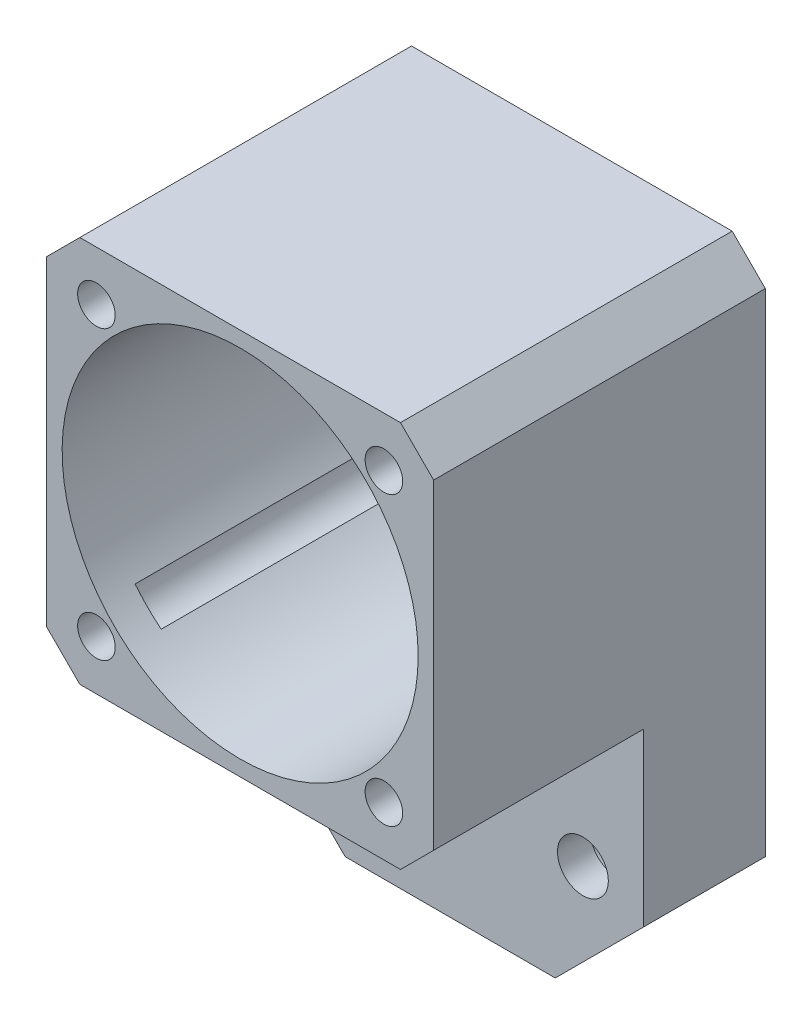
SolidWorks part; units mm, degrees
material "S235JR"
ref_plane "xy" through (0, 0, 0) normal (0, 0, 1) x (1, 0, 0)
ref_plane "xz" through (0, 0, 0) normal (0, 1, 0) x (1, 0, 0)
ref_plane "yz" through (0, 0, 0) normal (1, 0, 0) x (0, 0, -1)
ref_axis "x" through (-22.55, 0, 0) along (1, 0, 0)
ref_axis "y" through (0, 24.15, 0) along (0, -1, 0)
ref_axis "z" through (0, 0, -1.65) along (0, 0, 1)
sketch "Skizze1" plane through (0, 0, 0) normal (0, 0, 1) x (1, 0, 0)
  line L0 (-12, -28) -> (12, -28) construction
  line L1 (-17.5, 17.5) -> (17.5, 17.5)
  line L2 (-17.5, 17.5) -> (-17.5, -38)
  line L3 (-17.5, -38) -> (17.5, -38)
  line L4 (17.5, 17.5) -> (17.5, -38)
  line L5 (-13, 13) -> (13, 13) construction
  line L6 (-13, 13) -> (-13, -13) construction
  line L7 (-13, -13) -> (13, -13) construction
  line L8 (13, 13) -> (13, -13) construction
  circle A0 centre (0, 0) radius 16.1
  circle A1 centre (-13, 13) radius 1.7
  circle A2 centre (13, 13) radius 1.7
  circle A3 centre (-13, -13) radius 1.7
  circle A4 centre (13, -13) radius 1.7
  circle A5 centre (-12, -28) radius 2.3
  circle A6 centre (12, -28) radius 2.3
  point P7 (0, -38)
  point P12 (0, 13)
  point P13 (-13, 0)
  point P23 (0, -28)
  dimension "D1" = 32.2
  dimension "D6" = 3.4
  dimension "D8" = 4.6
  dimension "D2" = 38
  dimension "D3" = 17.5
  dimension "D4" = 35
  dimension "D5" = 26
  dimension "D7" = 10
  dimension "D9" = 24
extrude "Aufsatz-Linear austragen1" add sketch "Skizze1" along normal blind 11
sketch "Skizze2" plane through (0, 0, 11) normal (0, 0, 1) x (1, 0, 0)
  line L1 (-17.5, 17.5) -> (17.5, 17.5)
  line L2 (-17.5, 17.5) -> (-17.5, -17.5)
  line L3 (-17.5, -17.5) -> (17.5, -17.5)
  line L4 (17.5, 17.5) -> (17.5, -17.5)
  circle A0 centre (0, 0) radius 16.1 construction
  circle A1 centre (0, 0) radius 16.1
  circle A2 centre (13, 13) radius 1.7 construction
  circle A3 centre (13, -13) radius 1.7 construction
  circle A4 centre (-13, -13) radius 1.7 construction
  circle A5 centre (-13, 13) radius 1.7 construction
  circle A6 centre (13, 13) radius 1.7
  circle A7 centre (13, -13) radius 1.7
  circle A8 centre (-13, -13) radius 1.7
  circle A9 centre (-13, 13) radius 1.7
extrude "Aufsatz-Linear austragen2" add sketch "Skizze2" along normal blind 19
sketch "Skizze4" plane through (0, 0, 0) normal (0, 0, 1) x (1, 0, 0)
  circle A0 centre (-12, -28) radius 4
  circle A1 centre (12, -28) radius 4
  dimension "D1" = 8
extrude "Schnitt-Linear austragen1" cut sketch "Skizze4" along normal offset from surface (8 mm away) 3 up to face at (0, -27.75, 11)
sketch "Skizze5" plane through (0, 0, 0) normal (0, 0, 1) x (1, 0, 0)
  circle A0 centre (-13, 13) radius 2.9
  circle A1 centre (13, 13) radius 2.9
  circle A2 centre (-13, -13) radius 2.9
  circle A3 centre (13, -13) radius 2.9
  dimension "D1" = 5.8
extrude "Schnitt-Linear austragen2" cut sketch "Skizze5" along normal offset from surface (27 mm away) 3 up to face at (-11.3, -13, 30)
chamfer "Fase1" distance 3 angle 45 4 edges at (-17.5, -17.5, 20.5) (-17.5, 17.5, 15) (17.5, -17.5, 20.5) (17.5, 17.5, 15)
chamfer "Fase2" distance 8 angle 45 2 edges at (-17.5, -38, 5.5) (17.5, -38, 5.5)
